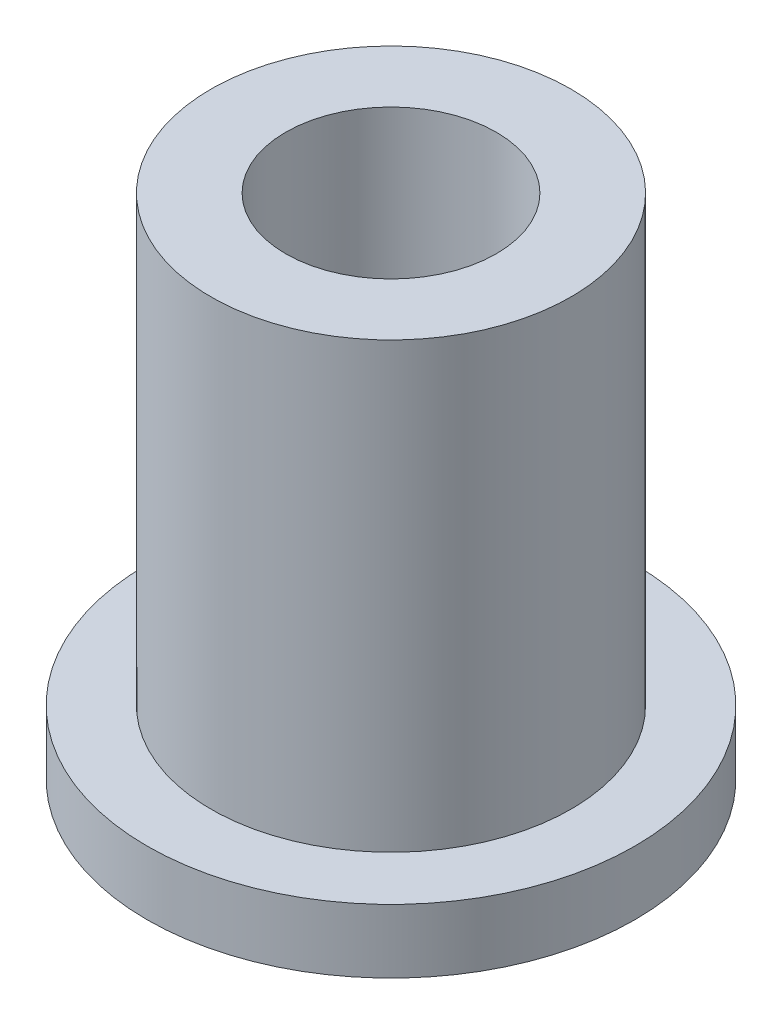
SolidWorks part; units mm, degrees
ref_plane "Front Plane" through (0, 0, 0) normal (0, 0, 1) x (1, 0, 0)
ref_plane "Top Plane" through (0, 0, 0) normal (0, 1, 0) x (1, 0, 0)
ref_plane "Right Plane" through (0, 0, 0) normal (1, 0, 0) x (0, 0, -1)
sketch "Sketch1" plane through (0, 0, 0) normal (1, 0, 0) x (0, 0, -1)
  line L0 (0, 0) -> (0, 8.4571) construction
  line L1 (0, 0) -> (3.82, 0)
  line L2 (3.82, 0) -> (3.82, 1)
  line L3 (3.82, 1) -> (2.82, 1)
  line L4 (2.82, 1) -> (2.82, 7.95)
  line L5 (2.82, 7.95) -> (0, 7.95)
  line L6 (0, 7.95) -> (0, 0)
  dimension "D1" = 7.95
  dimension "D2" = 5.64
  dimension "D3" = 1
  dimension "D4" = 1
revolve "Revolve1" add sketch "Sketch1" angle 360 about L0
hole_wizard "M4x0.7 Tapped Hole1" positions "3DSketch1" profile "Sketch2" tap size "M4x0.7" standard "ANSI Metric" end condition through all
sketch3d "3DSketch1"
  point P0 (0, 0, 0)
  point P3 (0, 0, 0)
sketch "Sketch2" plane through (0, 0, 0) normal (1, 0, 0) x (0, 0, -1)
  line L0 (0, 0) -> (0, 7.95)
  line L1 (0, 7.95) -> (1.65, 7.95)
  line L2 (1.65, 7.95) -> (1.65, 0)
  line L5 (1.65, 0) -> (0, 0)
  line L11 (0, -6.35) -> (0, 107.95) construction
  dimension "Thru Tap Drill Dia." = 3.3
  dimension "Thru Tap Drill Depth" = 7.95
cosmetic thread "Hole Thread4" parameters "D2"=4
